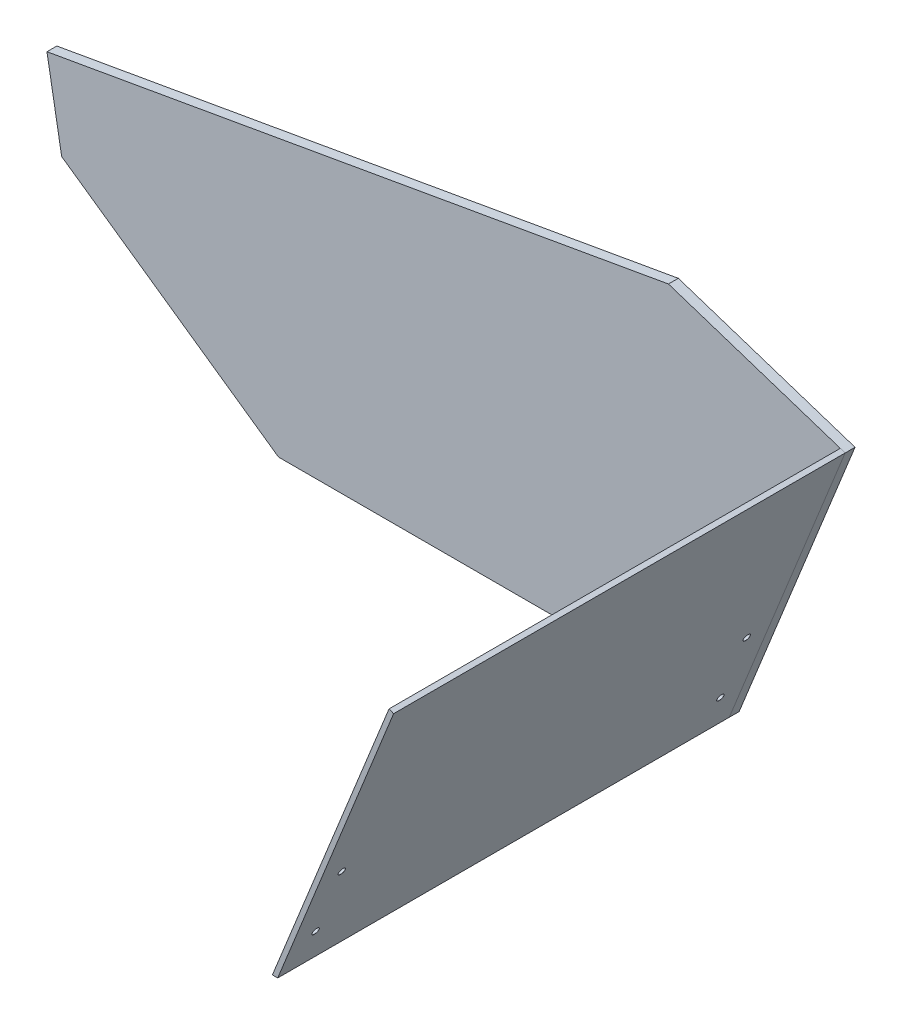
SolidWorks part; units mm, degrees
material "Melamine"
ref_plane "Front Plane" through (0, 0, 0) normal (0, 0, 1) x (1, 0, 0)
ref_plane "Top Plane" through (0, 0, 0) normal (0, 1, 0) x (1, 0, 0)
ref_plane "Right Plane" through (0, 0, 0) normal (1, 0, 0) x (0, 0, -1)
ref_axis "Axis1" through (0, 0, -14.8175) along (0, 0, 1)
sketch "Sketch1" plane through (0, 0, 0) normal (0, 0, 1) x (1, 0, 0)
  line L0 (-140, 0) -> (140, 0) construction
  line L1 (-140, 0) -> (-303.8304, 114.7153) construction
  line L4 (-151.0709, 0) -> (-307.4726, 109.5137) construction
  line L5 (-307.4726, 109.5137) -> (-303.8304, 114.7153) construction
  line L11 (140, 0) -> (143.4243, 0)
  line L12 (140, 0) -> (214.9213, 185.4368) construction
  line L14 (143.4243, 0) -> (217.8651, 184.2474)
  line L15 (217.8651, 184.2474) -> (214.9213, 185.4368)
  line L16 (214.9213, 185.4368) -> (140, 0)
  line L17 (-140, 0) -> (-151.0709, 0) construction
  point P4 (0, 0)
  dimension "D1" = 35
  dimension "D2" = 280
  dimension "D4" = 200
  dimension "D6" = 6.35
  dimension "D7" = 68
  dimension "D8" = 200
  dimension "D9" = 3.175
extrude "Boss-Extrude1" add sketch "Sketch1" along normal blind 290
sketch "Sketch2" plane through (0, 0, 0) normal (0, 0, 1) x (1, 0, 0)
  line L1 (-294.7779, 151.108) -> (104.3699, 221.4886)
  line L3 (143.4243, 0) -> (-146.0709, 0)
  line L4 (-146.0709, 0) -> (-285.3267, 97.508) construction
  line L5 (143.4243, 0) -> (217.8651, 184.2474)
  line L7 (-285.3267, 97.508) -> (-294.7779, 151.108)
  line L8 (-285.3267, 97.508) -> (-281.6845, 102.7096) construction
  line L9 (217.8651, 184.2474) -> (104.3699, 221.4886)
  line L10 (143.4243, 0) -> (104.3699, 221.4886) construction
  line L11 (-285.3267, 97.508) -> (-146.0709, 0)
  line L13 (-146.0709, 0) -> (-135, 0) construction
  line L14 (-285.3267, 97.508) -> (-146.0709, 0) construction
  line L15 (-281.6845, 102.7096) -> (-135, 0) construction
  dimension "D1" = 10
  dimension "D2" = 200
  dimension "D3" = 6.35
  dimension "D4" = 35
  dimension "D5" = 170
  dimension "D6" = 275
extrude "Boss-Extrude2" add sketch "Sketch2" against normal blind 6.35 separate body
ref_plane "HOLDING PLANE" through (0, 0, 0) normal (0.9848, 0.1736, 0) x (0, 0, 1)
ref_point "Walls Center"
hole_wizard "M4 Clearance Hole1" positions "Sketch3" profile "Sketch4" hole size "M4" standard "ANSI Metric" end condition through all
sketch "Sketch3" plane through (123.2976, -49.8155, 0) normal (0.9272, -0.3746, 0) x (0, 0, -1)
  line L0 (0, 53.7277) -> (0, 252.4449) construction
  line L1 (-290, 53.7277) -> (0, 53.7277) construction
  point P0 (-275, 123.7277)
  point P3 (-275, 78.7277)
  point P6 (-15, 123.7277)
  point P9 (-15, 78.7277)
  dimension "D1" = 15
  dimension "D2" = 25
sketch "Sketch4" plane through (169.6468, 64.9029, 275) normal (0, 0, 1) x (0.3746, 0.9272, 0)
  line L0 (0, 0) -> (0, 489.2651)
  line L1 (0, 489.2651) -> (2.25, 489.2651)
  line L2 (2.25, 489.2651) -> (2.25, 0.025)
  line L3 (2.25, 0.025) -> (2.275, 0)
  line L5 (2.275, 0) -> (0, 0)
  line L6 (-2.25, 0.025) -> (-2.275, 0) construction
  line L11 (0, -6.35) -> (0, 107.95) construction
  dimension "Thru Hole Dia." = 4.5
  dimension "Thru Hole Depth" = 489.2651
  dimension "Near C'Sink Dia." = 4.55
  dimension "Near C'Sink Angle" = 90
